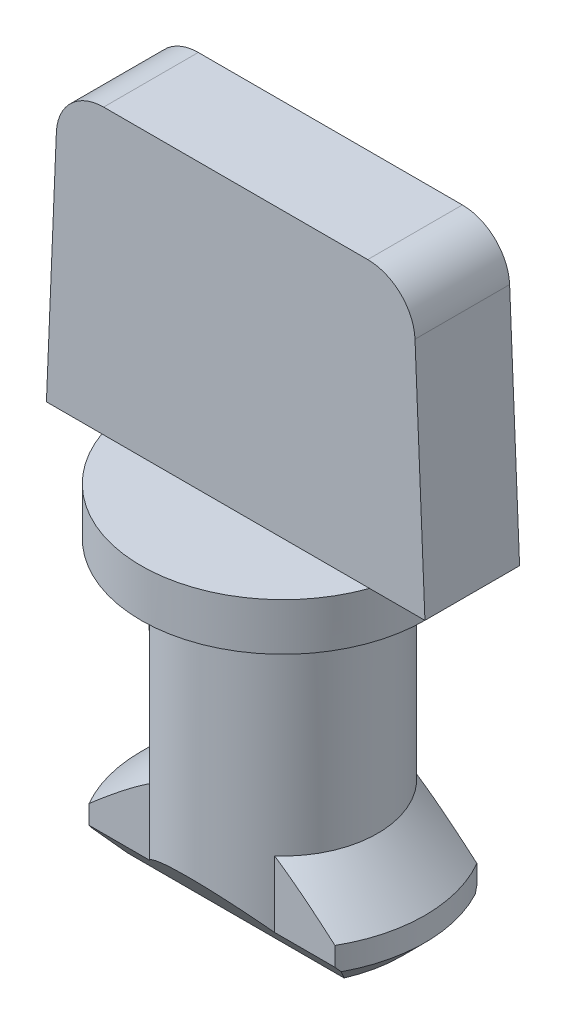
SolidWorks part; units mm, degrees
ref_plane "前视基准面" through (0, 0, 0) normal (0, 0, 1) x (1, 0, 0)
ref_plane "上视基准面" through (0, 0, 0) normal (0, 1, 0) x (1, 0, 0)
ref_plane "右视基准面" through (0, 0, 0) normal (1, 0, 0) x (0, 0, -1)
sketch "草图1" plane through (0, 0, 0) normal (0, 1, 0) x (1, 0, 0)
  circle A0 centre (0, 0) radius 3
extrude "凸台-拉伸1" add sketch "草图1" along normal blind 1
sketch "草图2" plane through (0, 0, 0) normal (0, 0, 1) x (1, 0, 0)
  line L0 (-3.75, 7) -> (3.75, 7)
  line L1 (-4, 1) -> (4, 1)
  line L2 (-3.75, 7) -> (-4, 1)
  line L3 (3.75, 7) -> (4, 1)
extrude "凸台-拉伸2" add sketch "草图2" along normal blind 1 and the other way blind 1
fillet "圆角1" radius 1 2 edges at (-3.75, 7, 0) (3.75, 7, 0)
sketch "草图3" plane through (0, 0, 0) normal (0, -1, 0) x (-1, 0, 0)
  circle A0 centre (0, 0) radius 2
extrude "凸台-拉伸3" add sketch "草图3" along normal blind 6.4
sketch "草图4" plane through (0, -6.4, 0) normal (0, -1, 0) x (-1, 0, 0)
  line L1 (2.5981, -1.5) -> (-2.5981, -1.5)
  line L3 (2.5981, 1.5) -> (-2.5981, 1.5)
  arc A0 (2.5981, -1.5) -> (2.5981, 1.5) centre (0, 0) ccw
  arc A1 (-2.5981, 1.5) -> (-2.5981, -1.5) centre (0, 0) ccw
extrude "凸台-拉伸4" add sketch "草图4" against normal blind 2
chamfer "倒角1" distance 0.5 angle 45 2 edges at (3, -6.4, 0) (-3, -6.4, 0)
chamfer "倒角2" distance 1 angle 45 2 edges at (3, -4.4, 0) (-3, -4.4, 0)
sketch "草图5" plane through (0, 0, 0) normal (1, 0, 0) x (0, 0, -1)
  line L0 (0, -6.4154) -> (0, -4.8208) construction
  line L1 (-1.5, -6.4) -> (1.5, -6.4) construction
  line L2 (2, -5.2) -> (1, -6.4)
  line L3 (-2, 0) -> (-2, -6.4) construction
  line L4 (-2, -5.2) -> (-2, -6.4)
  line L5 (-2, -6.4) -> (-1, -6.4)
  line L6 (-2, -5.2) -> (-1, -6.4)
  line L7 (2, -6.4) -> (1, -6.4)
  line L8 (2, -5.2) -> (2, -6.4)
extrude "切除-拉伸1" cut sketch "草图5" against normal up to next and the other way up to next
